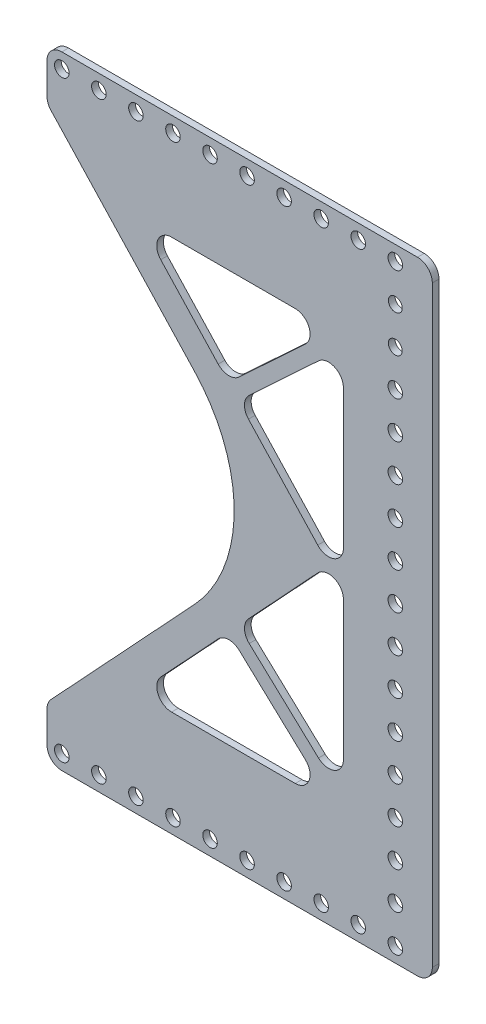
SolidWorks part; units mm, degrees
material "6061 Alloy"
ref_plane "Front Plane" through (0, 0, 0) normal (0, 0, 1) x (1, 0, 0)
ref_plane "Top Plane" through (0, 0, 0) normal (0, 1, 0) x (1, 0, 0)
ref_plane "Right Plane" through (0, 0, 0) normal (1, 0, 0) x (0, 0, -1)
sketch "Sketch1" plane through (0, 0, 0) normal (0, 0, 1) x (1, 0, 0)
  line L0 (238.8067, 781.2872) -> (222.2967, 781.2872)
  line L4 (176.5767, 781.2872) -> (116.8867, 781.2872)
  line L5 (113.1687, 754.4243) -> (162.3479, 701.6037)
  line L6 (243.8867, 776.2072) -> (243.8867, 666.9872)
  line L7 (111.8067, 757.8859) -> (111.8067, 776.2072)
  line L8 (150.787, 728.9305) -> (170.4738, 707.786)
  line L9 (213.4067, 674.5852) -> (213.4067, 722.2064)
  line L10 (196.902, 737.4722) -> (154.5049, 737.4722)
  line L11 (243.8867, 557.7672) -> (243.8867, 666.9872)
  line L12 (238.8067, 552.6872) -> (222.2967, 552.6872)
  line L16 (113.1687, 579.55) -> (162.3479, 632.3706)
  line L17 (176.5767, 552.6872) -> (116.8867, 552.6872)
  line L18 (111.8067, 576.0884) -> (111.8067, 557.7672)
  line L19 (200.3636, 728.6742) -> (177.6534, 707.5296)
  line L20 (180.8588, 637.3423) -> (204.6087, 662.8508)
  line L21 (204.8651, 725.9243) -> (181.1151, 703.8117)
  line L22 (180.8588, 696.632) -> (204.6087, 671.1235)
  line L23 (213.4067, 659.3892) -> (213.4067, 611.768)
  line L24 (204.8651, 608.05) -> (181.1151, 630.1627)
  line L25 (200.3636, 605.3001) -> (177.6534, 626.4447)
  line L26 (150.787, 605.0438) -> (170.4738, 626.1884)
  line L27 (196.902, 596.5022) -> (154.5049, 596.5022)
  line L28 (222.2967, 552.6872) -> (176.5767, 552.6872)
  line L29 (222.2967, 781.2872) -> (176.5767, 781.2872)
  arc A0 (238.8067, 781.2872) -> (243.8867, 776.2072) centre (238.8067, 776.2072) cw
  arc A5 (116.8867, 781.2872) -> (111.8067, 776.2072) centre (116.8867, 776.2072) ccw
  circle A6 centre (142.2867, 768.5872) radius 2.4892
  circle A7 centre (154.9867, 768.5872) radius 2.4892
  circle A8 centre (167.6867, 768.5872) radius 2.4892
  circle A9 centre (231.1867, 743.1872) radius 2.3719
  circle A10 centre (231.1867, 730.4872) radius 2.4892
  circle A11 centre (231.1867, 717.7872) radius 2.4892
  circle A12 centre (231.1867, 705.0872) radius 2.4892
  circle A13 centre (231.1867, 692.3872) radius 2.4892
  arc A14 (113.1687, 754.4243) -> (111.8067, 757.8859) centre (116.8867, 757.8859) cw
  arc A15 (204.6087, 671.1235) -> (213.4067, 674.5852) centre (208.3267, 674.5852) ccw
  arc A16 (150.787, 728.9305) -> (154.5049, 737.4722) centre (154.5049, 732.3922) cw
  arc A17 (238.8067, 552.6872) -> (243.8867, 557.7672) centre (238.8067, 557.7672) ccw
  circle A22 centre (167.6867, 565.3872) radius 2.4892
  circle A23 centre (154.9867, 565.3872) radius 2.4892
  circle A24 centre (142.2867, 565.3872) radius 2.4892
  arc A25 (113.1687, 579.55) -> (111.8067, 576.0884) centre (116.8867, 576.0884) ccw
  arc A26 (116.8867, 552.6872) -> (111.8067, 557.7672) centre (116.8867, 557.7672) cw
  circle A27 centre (231.1867, 616.1872) radius 2.4892
  circle A28 centre (231.1867, 603.4872) radius 2.4892
  circle A29 centre (231.1867, 590.7872) radius 2.4892
  circle A30 centre (231.1867, 565.3872) radius 2.4892
  circle A31 centre (231.1867, 768.5872) radius 2.4892
  arc A32 (162.3479, 701.6037) -> (162.3479, 632.3706) centre (125.1681, 666.9872) cw
  circle A33 centre (231.1867, 654.2872) radius 2.4892
  circle A34 centre (231.1867, 641.5872) radius 2.4892
  circle A35 centre (231.1867, 628.8872) radius 2.4892
  circle A36 centre (116.8867, 768.5872) radius 2.4892
  circle A37 centre (129.5867, 768.5872) radius 2.4892
  circle A38 centre (129.5867, 565.3872) radius 2.4892
  circle A39 centre (116.8867, 565.3872) radius 2.4892
  arc A40 (181.1151, 703.8117) -> (180.8588, 696.632) centre (184.5767, 700.0937) ccw
  arc A41 (204.8651, 725.9243) -> (213.4067, 722.2064) centre (208.3267, 722.2064) cw
  arc A42 (200.3636, 728.6742) -> (196.902, 737.4722) centre (196.902, 732.3922) ccw
  arc A43 (177.6534, 707.5296) -> (170.4738, 707.786) centre (174.1918, 711.2476) cw
  arc A44 (204.6087, 662.8508) -> (213.4067, 659.3892) centre (208.3267, 659.3892) cw
  arc A45 (181.1151, 630.1627) -> (180.8588, 637.3423) centre (184.5767, 633.8806) cw
  arc A46 (204.8651, 608.05) -> (213.4067, 611.768) centre (208.3267, 611.768) ccw
  arc A47 (200.3636, 605.3001) -> (196.902, 596.5022) centre (196.902, 601.5822) cw
  arc A48 (177.6534, 626.4447) -> (170.4738, 626.1884) centre (174.1918, 622.7267) ccw
  arc A49 (150.787, 605.0438) -> (154.5049, 596.5022) centre (154.5049, 601.5822) ccw
  circle A50 centre (231.1867, 679.6872) radius 2.4892
  circle A51 centre (231.1867, 666.9872) radius 2.4892
  circle A52 centre (231.1867, 755.8872) radius 2.3719
  circle A53 centre (231.1867, 578.0872) radius 2.4892
  circle A54 centre (180.3867, 565.3872) radius 2.4892
  circle A55 centre (193.0867, 565.3872) radius 2.4892
  circle A56 centre (205.7867, 565.3872) radius 2.4892
  circle A57 centre (218.4867, 565.3872) radius 2.4892
  circle A58 centre (180.3867, 768.5872) radius 2.4892
  circle A59 centre (193.0867, 768.5872) radius 2.4892
  circle A60 centre (205.7867, 768.5872) radius 2.4892
  circle A61 centre (218.4867, 768.5872) radius 2.4892
  point P14 (243.8867, 666.9872)
  point P17 (218.4867, 666.9872)
  dimension "D1" = 5
  dimension "D2" = 5
extrude "Boss-Extrude1" add sketch "Sketch1" along normal blind 2.286
sketch "Sketch2" [suppressed] plane through (0, 0, 2.286) normal (0, 0, 1) x (1, 0, 0)
  line L1 (243.8867, 666.9872) -> (166.9629, 666.9872) construction
  line L2 (243.8867, 557.7672) -> (243.8867, 776.2072) construction
  circle A0 centre (164.6497, 729.7313) radius 2.54
  circle A1 centre (181.8544, 724.0904) radius 2.54
  circle A2 centre (198.8305, 691.9777) radius 2.54
  circle A3 centre (204.3595, 709.5031) radius 2.54
  circle A5 centre (198.8305, 641.9966) radius 2.54
  circle A6 centre (204.3595, 624.4712) radius 2.54
  circle A7 centre (181.8544, 609.8839) radius 2.54
  circle A8 centre (164.6497, 604.243) radius 2.54
  dimension "D1" = 5.08
sketch "Sketch3" plane through (0, 0, 2.286) normal (0, 0, 1) x (1, 0, 0)
  line L0 (111.8067, 773.6672) -> (243.8867, 773.6672)
  line L1 (111.8067, 776.2072) -> (111.8067, 757.8859) construction
  line L2 (243.8867, 557.7672) -> (243.8867, 776.2072) construction
  line L3 (111.8067, 560.3072) -> (243.8867, 560.3072)
  line L4 (238.8067, 781.2872) -> (116.8867, 781.2872) construction
  line L5 (116.8867, 552.6872) -> (238.8067, 552.6872) construction
  line L6 (111.8067, 576.0884) -> (111.8067, 557.7672) construction
  line L7 (116.8867, 552.6872) -> (238.8067, 552.6872)
  line L8 (111.8067, 576.0884) -> (111.8067, 557.7672)
  line L9 (243.8867, 557.7672) -> (243.8867, 776.2072)
  line L10 (238.8067, 781.2872) -> (116.8867, 781.2872)
  line L11 (111.8067, 776.2072) -> (111.8067, 757.8859)
  arc A1 (116.8867, 781.2872) -> (111.8067, 776.2072) centre (116.8867, 776.2072) ccw construction
  arc A2 (243.8867, 776.2072) -> (238.8067, 781.2872) centre (238.8067, 776.2072) ccw construction
  arc A3 (238.8067, 552.6872) -> (243.8867, 557.7672) centre (238.8067, 557.7672) ccw construction
  arc A4 (111.8067, 557.7672) -> (116.8867, 552.6872) centre (116.8867, 557.7672) ccw construction
  arc A5 (238.8067, 552.6872) -> (243.8867, 557.7672) centre (238.8067, 557.7672) ccw
  arc A6 (111.8067, 557.7672) -> (116.8867, 552.6872) centre (116.8867, 557.7672) ccw
  arc A7 (243.8867, 776.2072) -> (238.8067, 781.2872) centre (238.8067, 776.2072) ccw
  arc A8 (116.8867, 781.2872) -> (111.8067, 776.2072) centre (116.8867, 776.2072) ccw
  dimension "D1" = 7.62
  dimension "D2" = 7.62
extrude "Cut-Extrude1" cut sketch "Sketch3" against normal through all contours L8 A6 L7 A5 L9 L3 | L10 A8 L11 L0 L9 A7 region at (177.8467, 777.4474, 2.286) region at (177.8467, 556.5269, 2.286)
fillet "Fillet1" radius 5.08 4 edges at (243.8867, 560.3072, 1.143) (111.8067, 560.3072, 1.143) (243.8867, 773.6672, 1.143) (111.8067, 773.6672, 1.143)
